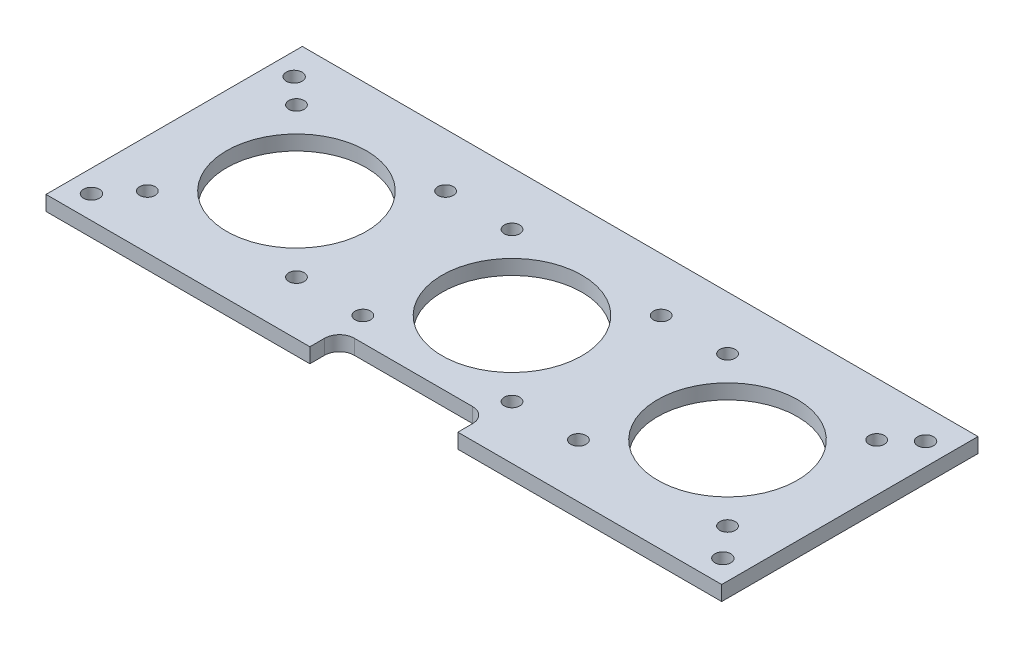
SolidWorks part; units mm, degrees
ref_plane "Front Plane" through (0, 0, 0) normal (0, 0, 1) x (1, 0, 0)
ref_plane "Top Plane" through (0, 0, 0) normal (0, 1, 0) x (1, 0, 0)
ref_plane "Right Plane" through (0, 0, 0) normal (1, 0, 0) x (0, 0, -1)
sketch "Sketch1" plane through (0, 0, 0) normal (0, 1, 0) x (1, 0, 0)
  line L0 (0, 0) -> (145, 55) construction
  line L1 (0, 0) -> (145, 0)
  line L2 (0, 0) -> (0, 55)
  line L3 (0, 55) -> (145, 55)
  line L4 (145, 0) -> (145, 55)
  point P5 (72.5, 27.5)
  dimension "D1" = 145
  dimension "D2" = 55
extrude "Boss-Extrude1" add sketch "Sketch1" along normal blind 3.175
ref_plane "Plane1" through (72.5, 0, 0) normal (1, 0, 0) x (0, 0, -1)
ref_plane "Plane2" through (0, 0, -27.5) normal (0, 0, -1) x (-1, 0, 0)
sketch "Sketch3" plane through (0, 3.175, 0) normal (0, 1, 0) x (1, 0, 0)
  line L0 (0, 0) -> (145, 55) construction
  point P4 (72.5, 27.5)
ref_axis "Axis1" through (72.5, 3.175, -27.5) along (0, 1, 0)
sketch "Sketch4" plane through (0, 0, 0) normal (0, -1, 0) x (1, 0, 0)
  line L0 (6.25, -7.5) -> (6.25, -47.5) construction
  line L1 (6.25, -47.5) -> (46.25, -47.5) construction
  line L2 (46.25, -47.5) -> (46.25, -7.5) construction
  line L3 (46.25, -7.5) -> (6.25, -7.5) construction
  line L4 (52.5, -7.5) -> (52.5, -47.5) construction
  line L5 (52.5, -47.5) -> (92.5, -47.5) construction
  line L6 (92.5, -47.5) -> (92.5, -7.5) construction
  line L7 (92.5, -7.5) -> (52.5, -7.5) construction
  line L8 (98.75, -7.5) -> (98.75, -47.5) construction
  line L9 (98.75, -47.5) -> (138.75, -47.5) construction
  line L10 (138.75, -47.5) -> (138.75, -7.5) construction
  line L11 (138.75, -7.5) -> (98.75, -7.5) construction
  line L12 (6.25, -7.5) -> (6.25, -47.5) construction
  line L13 (6.25, -47.5) -> (46.25, -47.5) construction
  line L14 (46.25, -47.5) -> (46.25, -7.5) construction
  line L15 (46.25, -7.5) -> (6.25, -7.5) construction
  line L16 (52.5, -7.5) -> (52.5, -47.5) construction
  line L17 (52.5, -47.5) -> (92.5, -47.5) construction
  line L18 (92.5, -47.5) -> (92.5, -7.5) construction
  line L19 (92.5, -7.5) -> (52.5, -7.5) construction
  line L20 (98.75, -7.5) -> (98.75, -47.5) construction
  line L21 (98.75, -47.5) -> (138.75, -47.5) construction
  line L22 (138.75, -47.5) -> (138.75, -7.5) construction
  line L23 (138.75, -7.5) -> (98.75, -7.5) construction
  line L24 (72.5, -55) -> (72.5, 0) construction
  line L25 (145, -55) -> (0, -55) construction
  line L26 (0, 0) -> (145, 0) construction
  line L27 (85.2, -3.175) -> (59.8, -3.175) construction
  line L28 (85.2, -6.35) -> (59.8, -6.35)
  line L29 (88.375, 0) -> (56.625, 0)
  line L30 (56.625, -3.175) -> (56.625, 0)
  line L31 (88.375, -3.175) -> (88.375, 0)
  circle A0 centre (10.25, -11.5) radius 1.651 construction
  circle A1 centre (10.25, -43.5) radius 1.651 construction
  circle A2 centre (42.25, -43.5) radius 1.651 construction
  circle A3 centre (26.25, -27.5) radius 15 construction
  circle A4 centre (42.25, -11.5) radius 1.651 construction
  circle A5 centre (56.5, -11.5) radius 1.651 construction
  circle A6 centre (56.5, -43.5) radius 1.651 construction
  circle A7 centre (88.5, -43.5) radius 1.651 construction
  circle A8 centre (88.5, -11.5) radius 1.651 construction
  circle A9 centre (72.5, -27.5) radius 15 construction
  circle A10 centre (102.75, -11.5) radius 1.651 construction
  circle A11 centre (102.75, -43.5) radius 1.651 construction
  circle A12 centre (134.75, -43.5) radius 1.651 construction
  circle A13 centre (134.75, -11.5) radius 1.651 construction
  circle A14 centre (118.75, -27.5) radius 15 construction
  circle A15 centre (10.25, -11.5) radius 1.651
  circle A16 centre (10.25, -43.5) radius 1.651
  circle A17 centre (42.25, -43.5) radius 1.651
  circle A18 centre (26.25, -27.5) radius 15
  circle A19 centre (42.25, -11.5) radius 1.651
  circle A20 centre (56.5, -11.5) radius 1.651
  circle A21 centre (56.5, -43.5) radius 1.651
  circle A22 centre (88.5, -43.5) radius 1.651
  circle A23 centre (88.5, -11.5) radius 1.651
  circle A24 centre (72.5, -27.5) radius 15
  circle A25 centre (102.75, -11.5) radius 1.651
  circle A26 centre (102.75, -43.5) radius 1.651
  circle A27 centre (134.75, -43.5) radius 1.651
  circle A28 centre (134.75, -11.5) radius 1.651
  circle A29 centre (118.75, -27.5) radius 15
  circle A30 centre (4.75, -5) radius 1.7 construction
  circle A31 centre (4.75, -48.5) radius 1.7 construction
  circle A32 centre (140.25, -5) radius 1.7 construction
  circle A33 centre (140.25, -48.5) radius 1.7 construction
  circle A34 centre (4.75, -5) radius 1.7
  circle A35 centre (4.75, -48.5) radius 1.7
  circle A36 centre (140.25, -5) radius 1.7
  circle A37 centre (140.25, -48.5) radius 1.7
  arc A38 (85.2, -6.35) -> (88.375, -3.175) centre (85.2, -3.175) ccw
  arc A39 (56.625, -3.175) -> (59.8, -6.35) centre (59.8, -3.175) ccw
  point P77 (72.5, -3.175)
  dimension "D1" = 3.175
  dimension "D2" = 25.4
  dimension "D3" = 3.175
extrude "Cut-Extrude1" cut sketch "Sketch4" against normal through all
equation "\"D3@Sketch4\"=\"D1@Sketch4\""
